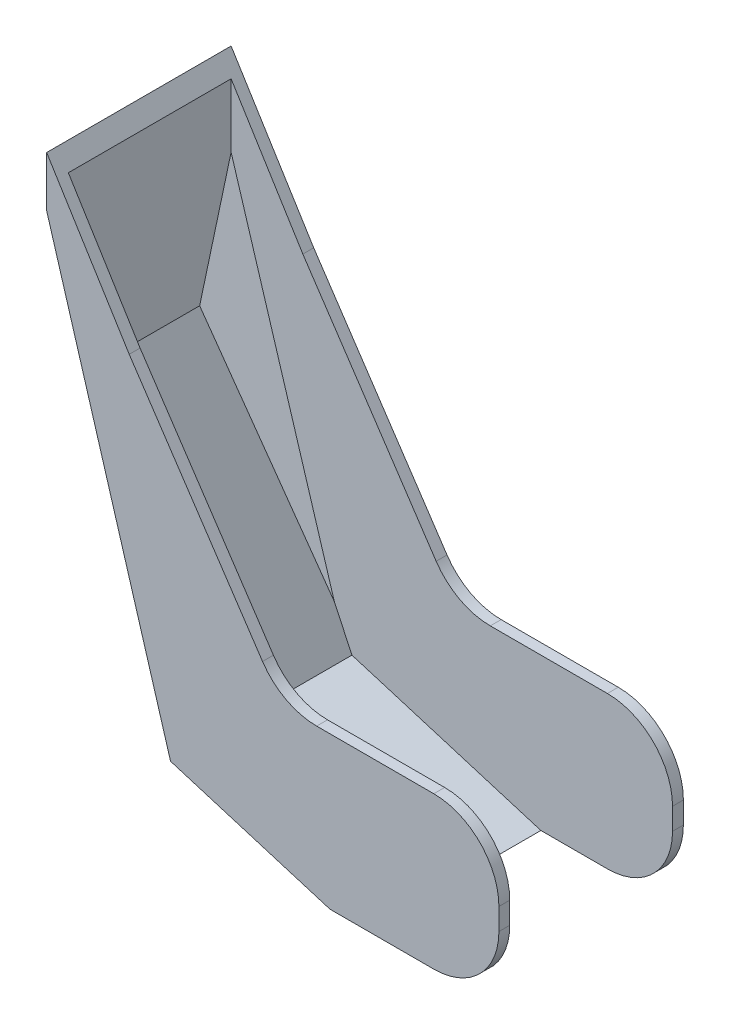
SolidWorks part; units mm, degrees
ref_plane "Front Plane" through (0, 0, 0) normal (0, 0, 1) x (1, 0, 0)
ref_plane "Top Plane" through (0, 0, 0) normal (0, 1, 0) x (1, 0, 0)
ref_plane "Right Plane" through (0, 0, 0) normal (1, 0, 0) x (0, 0, -1)
sketch "Sketch1" plane through (0, 0, 0) normal (0, 0, 1) x (1, 0, 0)
  line L0 (-15, 0) -> (-41.9864, 0)
  line L1 (-54.4549, 6.6613) -> (-85.1671, 52.5838)
  line L2 (-104.1967, 37.0771) -> (-104.1967, 83.3389)
  line L3 (-104.1967, 37.0771) -> (-75.6482, -23.8493)
  line L4 (-75.6482, -23.8493) -> (-50, -35)
  line L5 (-50, -35) -> (-15, -35)
  line L6 (0, -20) -> (0, -15)
  line L7 (-104.1967, 83.3389) -> (-85.1671, 52.5838)
  arc A0 (-15, 0) -> (0, -15) centre (-15, -15) cw
  arc A1 (-41.9864, 0) -> (-54.4549, 6.6613) centre (-41.9864, 15) cw
  arc A3 (-15, -35) -> (0, -20) centre (-15, -20) ccw
  point P10 (0, 0)
  point P13 (-50, 0)
  point P19 (0, -35)
  dimension "D6" = 15
  dimension "D8" = 15
  dimension "D1" = 15
  dimension "D3" = 35
  dimension "D4" = 50
  dimension "D5" = 50
extrude "Boss-Extrude1" add sketch "Sketch1" along normal blind 42.5
sketch "Sketch2" plane through (-71.1922, -33.3589, 0) normal (-0.9055, -0.4243, 0) x (0, 0, 1)
  line L0 (0, 10.5018) -> (16.357, 137.0618)
  line L1 (16.357, 137.0618) -> (25.357, 137.0618)
  line L2 (25.357, 137.0618) -> (42.5, 10.5018)
  line L3 (42.5, 10.5018) -> (0, 10.5018)
  dimension "D1" = 9
extrude "Cut-Extrude2" cut sketch "Sketch2" against normal blind 300 draft 42 flip side to cut
shell "Shell1" thickness 2.5 removed face at (-26.9658, -35, 21.25) removed face at (-5.9467, -29.0533, 21.25) removed face at (0, -17.5, 21.25) removed face at (-5.9467, -5.9467, 21.25) removed face at (-28.4932, 0, 21.25) removed face at (-48.6376, 2.5502, 21.25) removed face at (-69.811, 29.6225, 21.25) removed face at (-94.6819, 67.9614, 21.25)
